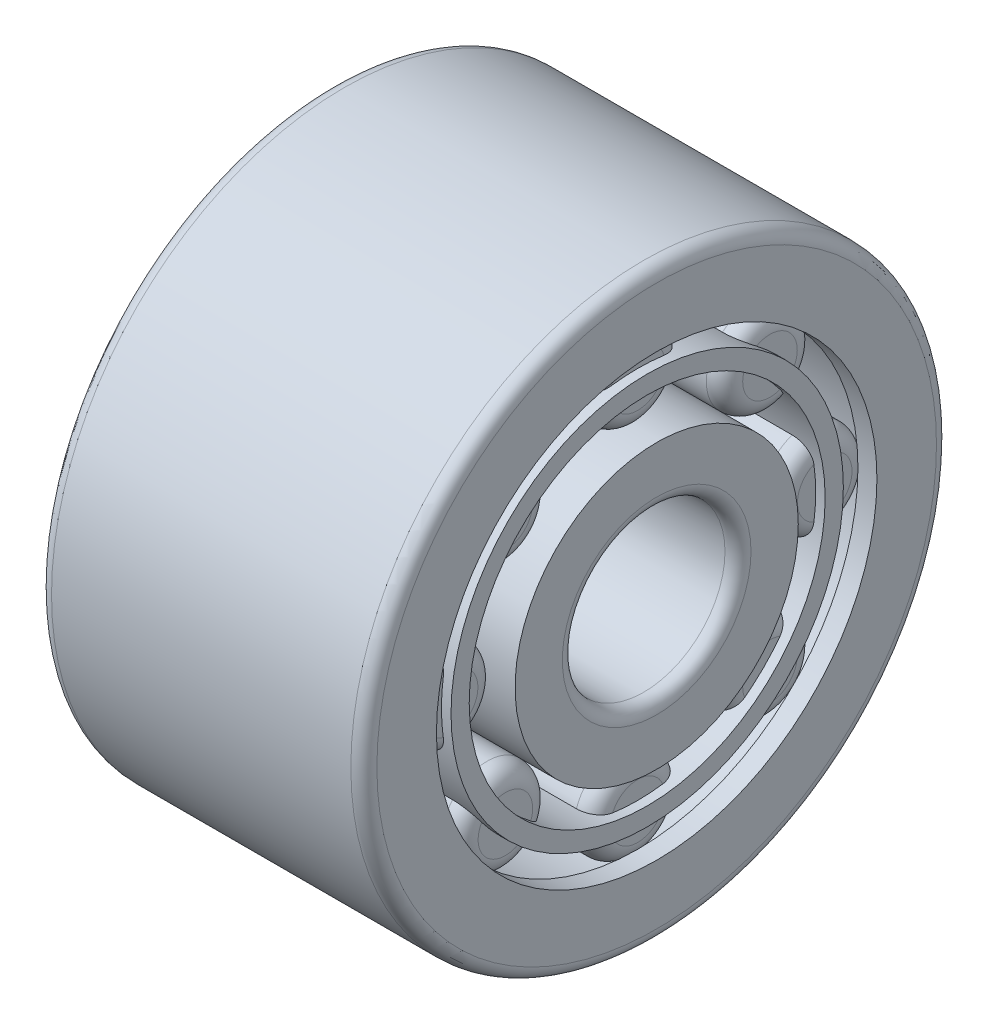
SolidWorks part; units mm, degrees
ref_plane "Plane1" through (0, 0, 0) normal (0, 0, 1) x (1, 0, 0)
ref_plane "Plane2" through (0, 0, 0) normal (0, 1, 0) x (1, 0, 0)
ref_plane "Plane3" through (0, 0, 0) normal (1, 0, 0) x (0, 0, -1)
sketch "Clipboard" plane through (0, 0, 0) normal (0, 0, 1) x (1, 0, 0)
  line L0 (-10, 0) -> (10, 0) construction
  line L1 (0, 0) -> (27.3694, -3.8465)
  line L2 (0, 0) -> (36.1572, 5.0816)
  line L3 (0, 0) -> (44.9449, -6.3166)
  line L4 (0, 0) -> (-22.3471, -0.7804)
  dimension "Race_OD" = 45.3866
  dimension "Race_ID" = 27.6384
sketch "OutRacSke" plane through (0, 0, 0) normal (0, 0, 1) x (1, 0, 0)
  line L0 (-14.0229, 22.6933) -> (-14.0229, 21.4933)
  line L1 (-14.0229, 21.4933) -> (-15.875, 21.4933)
  line L2 (-15.875, 21.4933) -> (-15.875, 27.305)
  line L3 (-14.605, 28.575) -> (14.605, 28.575)
  line L4 (15.875, 27.305) -> (15.875, 21.4933)
  line L5 (15.875, 21.4933) -> (14.0229, 21.4933)
  line L6 (14.0229, 21.4933) -> (14.0229, 22.6933)
  line L7 (14.0229, 22.6933) -> (-14.0229, 22.6933)
  line L8 (-7.9375, 0) -> (7.9375, 0) construction
  arc A0 (-15.875, 27.305) -> (-14.605, 28.575) centre (-14.605, 27.305) cw
  arc A1 (14.605, 28.575) -> (15.875, 27.305) centre (14.605, 27.305) cw
  dimension "D1" = 14.0229
  dimension "Groove_Dp" = 1.2
  dimension "Race_OD" = 45.3866
  dimension "Cyl_Len" = 28.0458
  dimension "halfWidth" = 15.875
revolve "OuterRace" add sketch "OutRacSke" angle 360 about L8 reverse direction yes
sketch "RolDetSke" plane through (0, 0, 0) normal (0, 0, 1) x (1, 0, 0)
  line L0 (-14.0229, 20.9188) -> (-14.0229, 18.2562)
  line L1 (-14.0229, 18.2562) -> (14.0229, 18.2562)
  line L2 (14.0229, 18.2562) -> (14.0229, 20.9188)
  line L3 (12.2479, 22.6938) -> (-12.2479, 22.6938)
  line L4 (-28.575, 18.2562) -> (28.575, 18.2562) construction
  arc A0 (14.0229, 20.9188) -> (12.2479, 22.6938) centre (12.2479, 20.9188) ccw
  arc A1 (-12.2479, 22.6938) -> (-14.0229, 20.9188) centre (-12.2479, 20.9188) ccw
  dimension "Cyl_Len" = 28.0458
  dimension "radius" = 1.775
  dimension "Roller_diameter" = 8.8751
revolve "RollerDetailed" add sketch "RolDetSke" angle 360 about L4 reverse direction yes
ref_axis "Axis1" through (-50, 0, 0) along (1, 0, 0)
sketch "RolSimSke" plane through (0, 25.4, 0) normal (0, 0, 1) x (1, 0, 0)
  line L0 (-14.0229, -4.4807) -> (-14.0229, -9.8058)
  line L1 (-25.4, -25.4) -> (25.4, -25.4) construction
  line L2 (14.0229, -9.8058) -> (14.0229, -4.4807)
  line L3 (12.2479, -2.7057) -> (-12.2479, -2.7057)
  line L5 (12.2479, -11.5808) -> (-12.2479, -11.5808)
  arc A0 (14.0229, -4.4807) -> (12.2479, -2.7057) centre (12.2479, -4.4807) ccw
  arc A1 (-12.2479, -2.7057) -> (-14.0229, -4.4807) centre (-12.2479, -4.4807) ccw
  arc A2 (14.0229, -9.8058) -> (12.2479, -11.5808) centre (12.2479, -9.8058) cw
  arc A3 (-12.2479, -11.5808) -> (-14.0229, -9.8058) centre (-12.2479, -9.8058) cw
  dimension "radius" = 1.775
  dimension "Roller_diameter" = 8.8751
  dimension "Cyl_Len" = 28.0458
revolve "RollersSimplified" [suppressed] add sketch "RolSimSke" angle 360 about L1
sketch "InsRacSke" plane through (0, 0, 0) normal (0, 0, 1) x (1, 0, 0)
  line L2 (-15.875, 13.8192) -> (-15.875, 9.2075)
  line L4 (-14.605, 7.9375) -> (14.605, 7.9375)
  line L5 (15.875, 9.2075) -> (15.875, 13.8192)
  line L8 (15.875, 13.8192) -> (-15.875, 13.8192)
  line L9 (-7.9375, 0) -> (7.9375, 0) construction
  arc A0 (-15.875, 9.2075) -> (-14.605, 7.9375) centre (-14.605, 9.2075) ccw
  arc A2 (14.605, 7.9375) -> (15.875, 9.2075) centre (14.605, 9.2075) ccw
  dimension "radius" = 1.27
  dimension "Bore" = 15.875
  dimension "halfWidth" = 15.875
  dimension "Race_ID" = 27.6384
revolve "InnerRace" add sketch "InsRacSke" angle 360 about L9 reverse direction yes
sketch "CagSpiSke" plane through (0, 0, 0) normal (0, 0, 1) x (1, 0, 0)
  line L0 (-17.1595, 0) -> (17.1595, 0) construction
  line L3 (-14.949, 17.3687) -> (14.949, 17.3687)
  line L4 (-14.949, 17.3687) -> (-14.949, 19.1438)
  line L5 (-14.949, 19.1438) -> (14.949, 19.1438)
  line L6 (14.949, 17.3687) -> (14.949, 19.1438)
revolve "CageSpine" add sketch "CagSpiSke" angle 360 about L0
pattern_circular "RollersDetailed" count 8 every 45 about axis through (-50, 0, 0) along (1, 0, 0) of "RollerDetailed"
equation "\"halfWidth@OutRacSke\" =  \"Width@OutRacSke\" / 2"
equation "\"CLdia@Clipboard\" =  ( \"Race_OD@Clipboard\" + \"Race_ID@Clipboard\" )  / 2"
equation "\"CLRad@RolDetSke\" = ( \"Race_OD@Clipboard\" + \"Race_ID@Clipboard\" )  / 4"
equation "\"Roller_diameter@RolDetSke\" =  ( \"Race_OD@Clipboard\" -  \"Race_ID@Clipboard\" )  / 2 + .001"
equation "\"Roller_diameter@RolSimSke\" = ( \"Race_OD@Clipboard\" -  \"Race_ID@Clipboard\" )  / 2 + .001"
equation "\"radius@RolDetSke\" = \"Roller_diameter@RolDetSke\" / 5"
equation "\"radius@RolSimSke\" = \"Roller_diameter@RolSimSke\" / 5"
equation "\"Cyl_Len@OutRacSke\" = \"Cyl_Len@RolDetSke\""
equation "\"Cyl_Len@RolSimSke\" = \"Cyl_Len@RolDetSke\""
equation "\"halfCylLen@RolDetSke\" = \"Cyl_Len@RolDetSke\" / 2"
equation "\"D1@OutRacSke\" = \"Cyl_Len@OutRacSke\" / 2"
equation "\"cage_width@CagSpiSke\" =  ( \"Cyl_Len@RolDetSke\" + \"Width@OutRacSke\" )  / 2"
equation "\"halfwidth@CagSpiSke\" = \"cage_width@CagSpiSke\" / 2"
equation "\"cage_thickness@CagSpiSke\" = \"Roller_diameter@RolDetSke\" / 5"
equation "\"d2@CagSpiSke\" = \"CLRad@RolDetSke\" * 2 - \"cage_thickness@CagSpiSke\""
equation "\"Max_count@Clipboard\" = int( 3.14159265 / atn(( \"Roller_diameter@RolDetSke\" / 2) / sqr( \"CLRad@RolDetSke\"  *  \"CLRad@RolDetSke\" - ( \"Roller_diameter@RolDetSke\" / 2) *  ( \"Roller_diameter@RolDetSke\" / 2))))"
equation "\"Max_count@Clipboard\" = ((sgn( \"Max_count@Clipboard\" - \"Count@Clipboard\" )-1)*( \"Max_count@Clipboard\" - \"Count@Clipboard\" ))/-2+ \"Count@Clipboard\""
equation "\"Count@RollersDetailed\" = int( \"Show_count@Clipboard\" ) "
equation "\"Count@RollersDetailed\" = ((sgn( \"Count@RollersDetailed\" - \"Max_count@Clipboard\" )-1)*( \"Count@RollersDetailed\" - \"Max_count@Clipboard\" ))/-2+ \"Max_count@Clipboard\""
equation "\"Count@RollersDetailed\" = ((sgn( \"Count@RollersDetailed\" - \"Min_count@Clipboard\" )+1)*( \"Count@RollersDetailed\" - \"Min_count@Clipboard\"))/2 +\"Min_count@Clipboard\""
equation "\"Angle@RollersDetailed\" = 360.0 / \"Max_count@Clipboard\""
equation "\"Bore@RolSimSke\" = \"Race_ID@Clipboard\""
equation "\"Race_ID@InsRacSke\" = \"Race_ID@Clipboard\""
equation "\"halfWidth@InsRacSke\" = \"Width_IR@InsRacSke\" / 2"
equation "\"halfLength@RolSimSke\" = \"Cyl_Len@RolSimSke\" / 2"
equation "\"Race_OD@OutRacSke\" = \"Race_OD@Clipboard\""
equation "\"Width_IR@InsRacSke\" = \"Width@OutRacSke\""
equation "\"Angle@CageSpine\" =  \"Angle@RollersDetailed\" * ( \"Count@RollersDetailed\" -1 + int( \"Count@RollersDetailed\" / \"Max_count@Clipboard\" ) )  + 0.001 -  int( \"Count@RollersDetailed\" / \"Max_count@Clipboard\" ) * 0.001"
equation "\"Angle@CageSpine\" =  \"Angle@CageSpine\" * int( \"Min_count@Clipboard\" / 2) + int(1 / \"Min_count@Clipboard\")  * 0.001"
equation "\"radius@InsRacSke\" = \"Radius@OutRacSke\""
